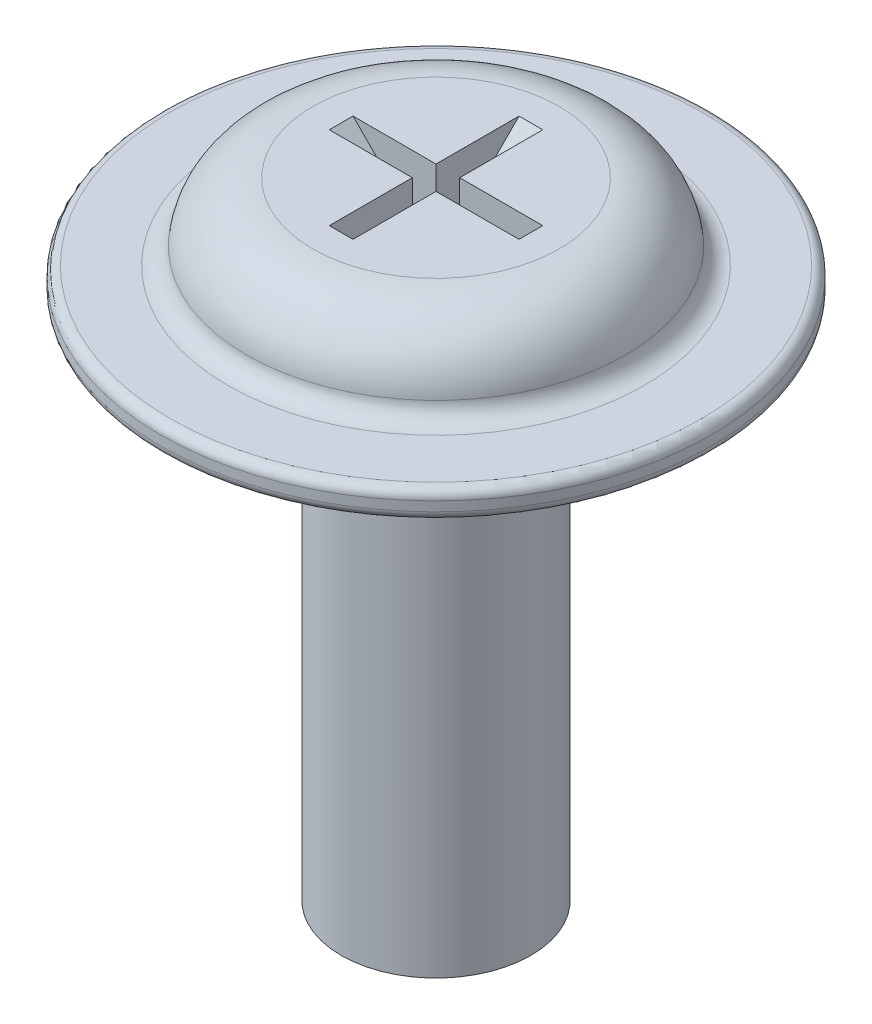
SolidWorks part; units mm, degrees
ref_plane "Front Plane" through (0, 0, 0) normal (0, 0, 1) x (1, 0, 0)
ref_plane "Top Plane" through (0, 0, 0) normal (0, 1, 0) x (1, 0, 0)
ref_plane "Right Plane" through (0, 0, 0) normal (1, 0, 0) x (0, 0, -1)
sketch "Sketch2" plane through (0, 0, 0) normal (0, 1, 0) x (1, 0, 0)
  circle A0 centre (0, 0) radius 2.9
  dimension "D1" = 5.8
extrude "Boss-Extrude1" add sketch "Sketch2" along normal blind 0.3
fillet "Fillet1" radius 0.1 1 edges at (0, 0.3, 2.9)
sketch "Sketch3" plane through (0, 0, 0) normal (0, 0, 1) x (1, 0, 0)
  line L0 (2.8, 0.3) -> (-2.8, 0.3) construction
  line L1 (2, 0.3) -> (0, 0.3)
  line L2 (0, 0.3) -> (0, 1.1)
  line L3 (0, 1.1) -> (1.3, 1.1)
  line L4 (2, 0.4) -> (2, 0.3)
  line L5 (0, 0) -> (0, -0.4595) construction
  arc A0 (2, 0.4) -> (1.3, 1.1) centre (1.3, 0.4) ccw
  point P9 (2, 1.1)
  dimension "D3" = 0.7
  dimension "D1" = 0.8
  dimension "D2" = 2
revolve "Revolve1" add sketch "Sketch3" angle 360 about L5
sketch "Sketch4" plane through (0, 0, 0) normal (0, -1, 0) x (1, 0, 0)
  circle A0 centre (0, 0) radius 1
  dimension "D1" = 2
extrude "Boss-Extrude2" add sketch "Sketch4" along normal blind 5.5
sketch "Sketch5" plane through (0, 1.1, 0) normal (0, 1, 0) x (1, 0, 0)
  line L0 (0, 0) -> (0, 0.8691) construction
  line L1 (0, 0) -> (0.9731, 0) construction
  line L2 (-0.125, 0.5) -> (0.125, 0.5)
  line L3 (0.125, 0.5) -> (0.125, 0.125)
  line L4 (0.125, 0.125) -> (0.5, 0.125)
  line L5 (0.5, 0.125) -> (0.5, -0.125)
  line L6 (-0.5, 0.125) -> (-0.5, -0.125)
  line L7 (-0.125, 0.125) -> (-0.5, 0.125)
  line L8 (-0.125, 0.5) -> (-0.125, 0.125)
  line L9 (0.125, -0.125) -> (0.5, -0.125)
  line L10 (0.125, -0.5) -> (0.125, -0.125)
  line L11 (-0.125, -0.5) -> (0.125, -0.5)
  line L12 (-0.125, -0.5) -> (-0.125, -0.125)
  line L13 (-0.125, -0.125) -> (-0.5, -0.125)
  point P13 (0, 0.5)
  point P14 (0.5, 0)
  point P19 (-0.5, 0)
  dimension "D1" = 0.5
  dimension "D2" = 0.5
  dimension "D3" = 0.25
  dimension "D4" = 0.25
extrude "Cut-Extrude1" cut sketch "Sketch5" against normal blind 0.5
chamfer "Chamfer2" distance 0.5 angle 45 4 edges at (-0.5, 1.1, 0) (0, 1.1, 0.5) (0.5, 1.1, 0) (0, 1.1, -0.5)
fillet "Fillet2" radius 0.2 1 edges at (0, 0.3, 2)
fillet "Fillet3" radius 0.1 1 edges at (0, 0, 2.9)
fillet "Fillet4" radius 0.1 1 edges at (0, 0, -1)
